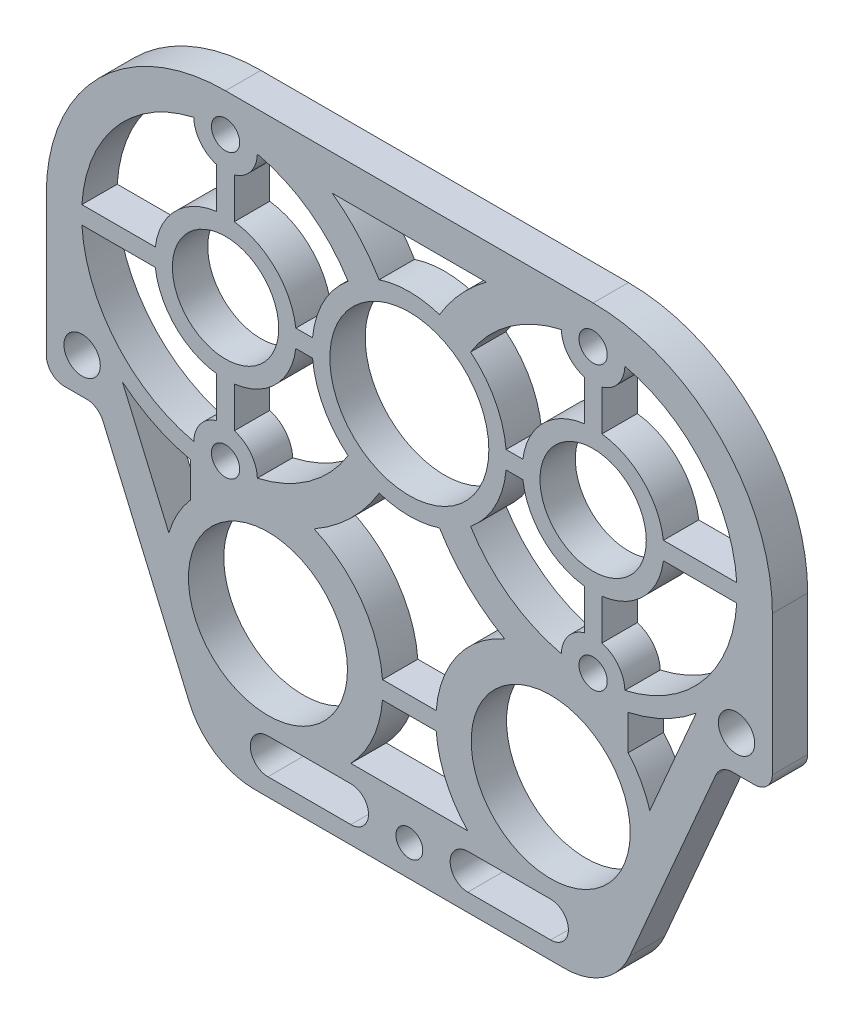
SolidWorks part; units mm, degrees
material "6061 Alloy"
ref_plane "Front Plane" through (0, 0, 0) normal (0, 0, 1) x (1, 0, 0)
ref_plane "Top Plane" through (0, 0, 0) normal (0, 1, 0) x (1, 0, 0)
ref_plane "Right Plane" through (0, 0, 0) normal (1, 0, 0) x (0, 0, -1)
sketch "Sketch1" plane through (0, 0, 0) normal (0, 0, 1) x (1, 0, 0)
  line L1 (-70.3836, -64.2939) -> (-83.566, -64.2939)
  line L2 (-59.3451, -45.9715) -> (-59.3451, -53.2554)
  line L3 (-59.3451, -85.7913) -> (-59.3451, -78.5074)
  line L4 (-56.1701, -45.9715) -> (-56.1701, -53.2554)
  line L5 (-45.1316, -64.2939) -> (-42.1278, -64.2939)
  line L6 (-56.1701, -85.7913) -> (-56.1701, -78.5074)
  line L7 (-70.3836, -67.4689) -> (-83.566, -67.4689)
  line L8 (-76.2768, -88.24) -> (-67.9444, -107.5697)
  line L9 (-45.1316, -67.4689) -> (-42.1278, -67.4689)
  line L10 (-64.0572, -94.2219) -> (-64.0572, -100.5164)
  line L11 (-69.0893, -120.875) -> (-60.9774, -139.773)
  line L12 (40.4896, -65.8814) -> (40.4896, -91.0025)
  line L13 (-29.5612, -111.198) -> (-19.9139, -111.198)
  line L14 (-14.2297, -127.073) -> (-35.2455, -127.073)
  line L15 (-29.5612, -114.373) -> (-19.9139, -114.373)
  line L16 (-57.7576, -33.6742) -> (8.2824, -33.6742)
  line L17 (-10.9194, -40.0242) -> (-38.5558, -40.0242)
  line L18 (14.582, -94.2219) -> (14.582, -100.5164)
  line L19 (-4.3436, -67.4689) -> (-7.3474, -67.4689)
  line L20 (26.8016, -88.24) -> (18.4692, -107.5697)
  line L21 (20.9084, -67.4689) -> (34.0908, -67.4689)
  line L22 (6.6949, -85.7913) -> (6.6949, -78.5074)
  line L23 (-4.3436, -64.2939) -> (-7.3474, -64.2939)
  line L24 (6.6949, -45.9715) -> (6.6949, -53.2554)
  line L25 (9.8699, -85.7913) -> (9.8699, -78.5074)
  line L26 (9.8699, -45.9715) -> (9.8699, -53.2554)
  line L27 (20.9084, -64.2939) -> (34.0908, -64.2939)
  line L28 (30.2994, -96.1669) -> (19.6141, -120.955)
  line L29 (-86.7453, -94.1419) -> (-82.7311, -94.1419)
  line L30 (-79.7746, -96.0869) -> (-69.0893, -120.875)
  line L31 (-60.9774, -139.773) -> (11.5022, -139.773)
  line L32 (-89.9648, -65.8814) -> (-89.9648, -90.9225)
  line L33 (19.6141, -120.955) -> (11.5022, -139.773)
  line L34 (-35.2455, -133.423) -> (-50.1376, -133.423) construction
  line L35 (-35.2455, -136.598) -> (-50.1376, -136.598)
  line L36 (-35.2455, -130.248) -> (-50.1376, -130.248)
  line L37 (0.6624, -133.423) -> (-14.2297, -133.423) construction
  line L38 (0.6624, -136.598) -> (-14.2297, -136.598)
  line L39 (0.6624, -130.248) -> (-14.2297, -130.248)
  line L40 (37.2702, -94.1419) -> (33.2559, -94.1419)
  circle A0 centre (-57.7576, -65.8814) radius 9.5504
  circle A1 centre (-57.7576, -40.4814) radius 2.54
  arc A2 (-41.8493, -93.8855) -> (-30.1579, -82.4814) centre (-57.7576, -65.8814) ccw
  circle A3 centre (-57.7576, -91.2814) radius 2.54
  circle A4 centre (-83.5259, -87.703) radius 3.2639
  arc A5 (-52.0455, -91.0998) -> (-56.1701, -85.7913) centre (-57.7576, -91.2814) ccw
  arc A6 (-52.0455, -91.0998) -> (-35.741, -79.4411) centre (-57.7576, -65.8814) ccw
  arc A7 (-52.0455, -40.663) -> (-56.1701, -45.9715) centre (-57.7576, -40.4814) cw
  arc A8 (-59.3451, -45.9715) -> (-63.4697, -40.663) centre (-57.7576, -40.4814) cw
  arc A9 (-56.1701, -78.5074) -> (-45.1316, -67.4689) centre (-57.7576, -65.8814) ccw
  arc A10 (-59.3451, -85.7913) -> (-63.4697, -91.0998) centre (-57.7576, -91.2814) ccw
  arc A11 (-83.566, -67.4689) -> (-63.4697, -91.0998) centre (-57.7576, -65.8814) ccw
  arc A12 (-59.3451, -53.2554) -> (-70.3836, -64.2939) centre (-57.7576, -65.8814) ccw
  circle A13 centre (-50.1376, -112.7855) radius 14.2875
  arc A14 (-70.3836, -67.4689) -> (-59.3451, -78.5074) centre (-57.7576, -65.8814) ccw
  arc A15 (-45.1316, -64.2939) -> (-56.1701, -53.2554) centre (-57.7576, -65.8814) ccw
  arc A16 (-63.4697, -40.663) -> (-83.566, -64.2939) centre (-57.7576, -65.8814) ccw
  arc A17 (-30.1579, -82.4814) -> (-19.3173, -82.4814) centre (-24.7376, -65.8814) ccw
  arc A18 (-64.0572, -100.5164) -> (-67.9444, -107.5697) centre (-50.1376, -112.7855) ccw
  arc A19 (-76.2768, -88.24) -> (-64.0572, -94.2219) centre (-57.7576, -65.8814) ccw
  circle A20 centre (-24.7376, -65.8814) radius 14.2875
  arc A21 (-35.741, -52.3218) -> (-42.1278, -64.2939) centre (-24.7376, -65.8814) ccw
  arc A22 (-35.741, -52.3218) -> (-52.0455, -40.663) centre (-57.7576, -65.8814) ccw
  arc A23 (-42.1278, -67.4689) -> (-35.741, -79.4411) centre (-24.7376, -65.8814) ccw
  arc A24 (-30.1579, -49.2814) -> (-38.5558, -40.0242) centre (-57.7576, -65.8814) ccw
  arc A25 (-19.3173, -49.2814) -> (-30.1579, -49.2814) centre (-24.7376, -65.8814) ccw
  arc A26 (-29.5612, -111.198) -> (-41.8493, -93.8855) centre (-50.1376, -112.7855) ccw
  arc A27 (-35.2455, -127.073) -> (-29.5612, -114.373) centre (-50.1376, -112.7855) ccw
  arc A28 (-57.7576, -33.6742) -> (-89.9648, -65.8814) centre (-57.7576, -65.8814) ccw
  arc A29 (8.2824, -33.6742) -> (40.4896, -65.8814) centre (8.2824, -65.8814) cw
  arc A30 (-14.2297, -127.073) -> (-19.9139, -114.373) centre (0.6624, -112.7855) cw
  arc A31 (-19.9139, -111.198) -> (-7.6259, -93.8855) centre (0.6624, -112.7855) cw
  arc A32 (-19.3173, -49.2814) -> (-10.9194, -40.0242) centre (8.2824, -65.8814) cw
  arc A33 (-7.3474, -67.4689) -> (-13.7342, -79.4411) centre (-24.7376, -65.8814) cw
  arc A34 (-13.7342, -52.3218) -> (2.5703, -40.663) centre (8.2824, -65.8814) cw
  arc A35 (-13.7342, -52.3218) -> (-7.3474, -64.2939) centre (-24.7376, -65.8814) cw
  arc A36 (26.8016, -88.24) -> (14.582, -94.2219) centre (8.2824, -65.8814) cw
  arc A37 (14.582, -100.5164) -> (18.4692, -107.5697) centre (0.6624, -112.7855) cw
  arc A38 (13.9945, -40.663) -> (34.0908, -64.2939) centre (8.2824, -65.8814) cw
  arc A39 (-4.3436, -64.2939) -> (6.6949, -53.2554) centre (8.2824, -65.8814) cw
  arc A40 (20.9084, -67.4689) -> (9.8699, -78.5074) centre (8.2824, -65.8814) cw
  circle A41 centre (0.6624, -112.7855) radius 14.2875
  arc A42 (9.8699, -53.2554) -> (20.9084, -64.2939) centre (8.2824, -65.8814) cw
  arc A43 (34.0908, -67.4689) -> (13.9945, -91.0998) centre (8.2824, -65.8814) cw
  arc A44 (9.8699, -85.7913) -> (13.9945, -91.0998) centre (8.2824, -91.2814) cw
  arc A45 (6.6949, -78.5074) -> (-4.3436, -67.4689) centre (8.2824, -65.8814) cw
  arc A46 (9.8699, -45.9715) -> (13.9945, -40.663) centre (8.2824, -40.4814) ccw
  arc A47 (2.5703, -40.663) -> (6.6949, -45.9715) centre (8.2824, -40.4814) ccw
  arc A48 (2.5703, -91.0998) -> (-13.7342, -79.4411) centre (8.2824, -65.8814) cw
  arc A49 (2.5703, -91.0998) -> (6.6949, -85.7913) centre (8.2824, -91.2814) cw
  arc A50 (-86.7453, -94.1419) -> (-89.9648, -90.9225) centre (-86.7453, -90.9225) cw
  circle A51 centre (8.2824, -91.2814) radius 2.54
  arc A52 (-7.6259, -93.8855) -> (-19.3173, -82.4814) centre (8.2824, -65.8814) cw
  circle A53 centre (8.2824, -40.4814) radius 2.54
  circle A54 centre (8.2824, -65.8814) radius 9.5504
  arc A55 (-35.2455, -136.598) -> (-35.2455, -130.248) centre (-35.2455, -133.423) ccw
  circle A56 centre (-24.7376, -134.185) radius 2.413
  arc A57 (-50.1376, -130.248) -> (-50.1376, -136.598) centre (-50.1376, -133.423) ccw
  arc A58 (0.6624, -136.598) -> (0.6624, -130.248) centre (0.6624, -133.423) ccw
  arc A59 (-14.2297, -130.248) -> (-14.2297, -136.598) centre (-14.2297, -133.423) ccw
  arc A60 (-79.7746, -96.0869) -> (-82.7311, -94.1419) centre (-82.7311, -97.3614) ccw
  arc A61 (30.2994, -96.1669) -> (33.2559, -94.1419) centre (33.2892, -97.3612) cw
  arc A62 (37.2702, -94.1419) -> (40.4896, -91.0025) centre (37.2711, -90.9225) ccw
  circle A63 centre (34.0507, -87.703) radius 3.2639
  point P3 (-24.7376, -65.8814)
  point P19 (-70.5223, -91.9569)
  point P34 (0, 0)
  point P48 (-24.7376, -127.073)
  point P50 (-15.8172, -133.423)
  point P51 (-24.7376, -111.198)
  point P54 (-24.7376, -111.198)
  point P57 (-24.7376, -114.373)
  point P58 (-24.7376, -33.6742)
  point P104 (-24.7376, -40.0242)
  point P109 (-60.9774, -139.773)
  point P112 (-42.6916, -133.423)
  point P113 (11.5022, -139.773)
  point P118 (-6.7836, -133.423)
  dimension "D2" = 19.1008
  dimension "D4" = 5.08
  dimension "D8" = 25.4
  dimension "D9" = 3.175
  dimension "D10" = 11.43
  dimension "D11" = 33.02
  dimension "D12" = 46.9041
  dimension "D13" = 25.4
  dimension "D14" = 3.2195
  dimension "D15" = 1.5875
  dimension "D17" = 5.715
  dimension "D18" = 28.575
  dimension "D23" = 1.5875
  dimension "D27" = 6.5278
  dimension "D7" = 64.4144
  dimension "D28" = 34.925
  dimension "D29" = 25.4508
  dimension "D30" = 51.7144
  dimension "D5" = 5.08
  dimension "D16" = 5.715
  dimension "D24" = 29.0322
  dimension "D25" = 28.575
  dimension "D26" = 3.2195
  dimension "D36" = 3.175
  dimension "D37" = 4.826
  dimension "D40" = 3.175
  dimension "D6" = 25.4
  dimension "D19" = 3.175
  dimension "D20" = 1.5875
  dimension "D31" = 3.175
  dimension "D21" = 33.02
  dimension "D22" = 3.175
  dimension "D32" = 1.5875
  dimension "D33" = 6.4389
  dimension "D34" = 6.35
  dimension "D35" = 26.9875
  dimension "D38" = 5.588
  dimension "D39" = 0
  dimension "D41" = 6.4389
  dimension "D42" = 52.07
  dimension "D43" = 6.4389
  dimension "D44" = 52.07
extrude "Boss-Extrude1" add sketch "Sketch1" along normal blind 6.35 contours A0 region at (-72.8878, -107.8153, 0)
fillet "Fillet1" radius 12.7 2 edges at (11.5022, -139.773, 3.175) (-60.9774, -139.773, 3.175)
